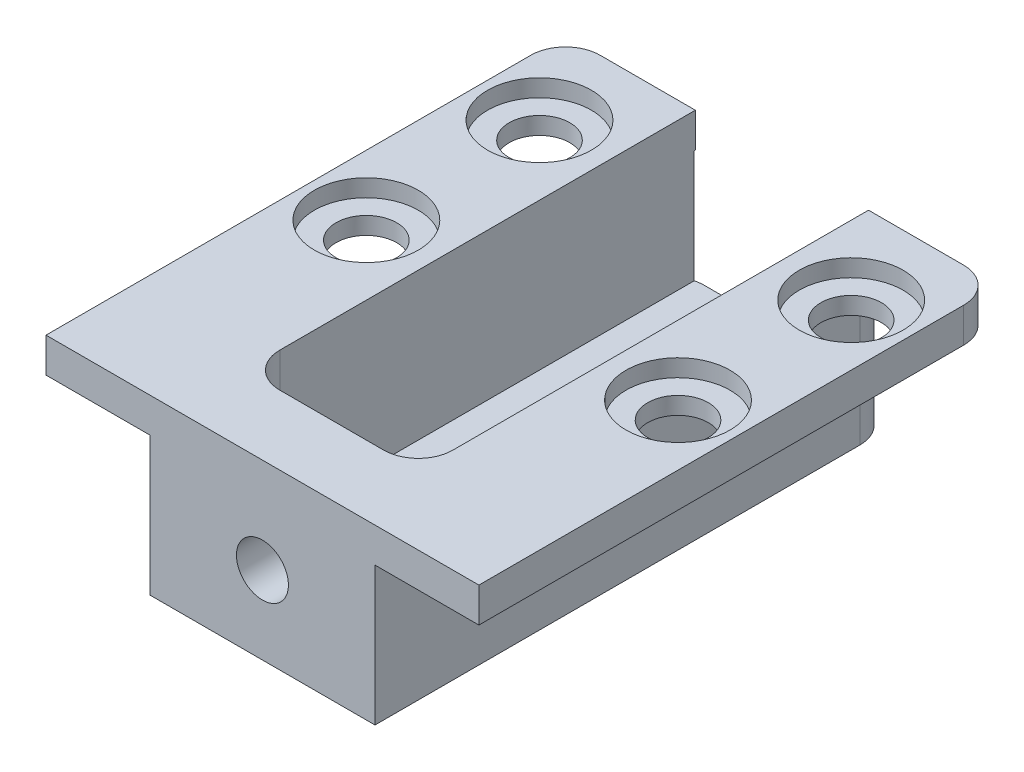
SolidWorks part; units mm, degrees
other "标注1"
sketch "草图19" plane through (-20.75, 4, 27.75) normal (0.0284, 0.9516, -0.306) x (-0.8925, -0.1137, -0.4365)
ref_plane "前视基准面" through (0, 0, 0) normal (0, 0, 1) x (1, 0, 0)
ref_plane "上视基准面" through (0, 0, 0) normal (0, 1, 0) x (1, 0, 0)
ref_plane "右视基准面" through (0, 0, 0) normal (1, 0, 0) x (0, 0, -1)
sketch "草图1" plane through (0, 0, 0) normal (0, 1, 0) x (1, 0, 0)
  line L1 (-17.5, -27.5) -> (17.5, -27.5)
  line L2 (-17.5, -27.5) -> (-17.5, 27.5)
  line L3 (-17.5, 27.5) -> (17.5, 27.5)
  line L4 (17.5, -27.5) -> (17.5, 27.5)
  line L5 (-17.5, -27.5) -> (17.5, 27.5) construction
  line L6 (-17.5, 27.5) -> (17.5, -27.5) construction
  point P0 (0, 0)
  dimension "D1" = 55
  dimension "D2" = 35
extrude "凸台-拉伸1" add sketch "草图1" along normal blind 1
sketch "草图2" plane through (0, 1, 0) normal (0, 1, 0) x (1, 0, 0)
  line L0 (-105.917, 0) -> (-62.25, 0) construction
  line L1 (106.75, 2.25) -> (121.75, 2.25)
  line L2 (-31.4474, 57.1013) -> (151.75, 26.6691)
  line L4 (124.0586, 2.6571) -> (154.0586, 13.5762)
  line L5 (-60.1618, 23.6059) -> (-42.6093, 52.0296)
  line L6 (121.75, 2.25) -> (121.75, 9) construction
  line L7 (121.75, -2.25) -> (121.75, -9) construction
  line L8 (-60.1618, -23.6059) -> (-42.6093, -52.0296)
  line L9 (124.0586, -2.6571) -> (154.0586, -13.5762)
  line L10 (121.75, -9) -> (128.5, -9)
  line L11 (-31.4474, -57.1013) -> (151.75, -26.6691)
  line L12 (106.75, -2.25) -> (121.75, -2.25)
  line L13 (-62.25, 16.25) -> (-62.25, -16.25)
  line L14 (106.75, 2.25) -> (106.75, -2.25)
  line L15 (106.75, 0) -> (124.0666, 0) construction
  arc A0 (-60.1618, 23.6059) -> (-62.25, 16.25) centre (-48.25, 16.25) ccw
  arc A1 (-31.4474, 57.1013) -> (-42.6093, 52.0296) centre (-33.25, 46.25) ccw
  arc A2 (121.75, 2.25) -> (124.0586, 2.6571) centre (121.75, 9) ccw
  arc A3 (154.0586, 13.5762) -> (151.75, 26.6691) centre (151.75, 19.9191) ccw
  arc A4 (154.0586, -13.5762) -> (151.75, -26.6691) centre (151.75, -19.9191) cw
  arc A5 (121.75, -2.25) -> (128.5, -9) centre (121.75, -9) cw
  arc A6 (-31.4474, -57.1013) -> (-42.6093, -52.0296) centre (-33.25, -46.25) cw
  arc A7 (-60.1618, -23.6059) -> (-62.25, -16.25) centre (-48.25, -16.25) cw
  line M10 (17.5, -27.5) -> (17.5, 27.5)
  line M11 (17.5, 27.5) -> (-17.5, 27.5)
  line M12 (-17.5, 27.5) -> (-17.5, -27.5)
  line M13 (-17.5, -27.5) -> (17.5, -27.5)
  dimension "D2" = 28
  dimension "D3" = 48.25
  dimension "D4" = 22
  dimension "D5" = 15
  dimension "D7" = 13.5
  dimension "D10" = 13.5
  dimension "D11" = 30
  dimension "D1" = 2.25
  dimension "D8" = 20
  dimension "D9" = 30
  dimension "D12" = 15
extrude "凸台-拉伸2" add sketch "草图2" along normal blind 3 contours A7 L8 A6 L11 A4 L9 A5 L12 L14 L1 A2 L4 A3 L2 A1 L5 A0 L13 | M13 M10 M11 M12 region at (37.3678, 1, 0) region at (0, 1, 0)
sketch "草图3" plane through (0, 4, 0) normal (0, 1, 0) x (1, 0, 0)
  circle A0 centre (-48.25, 16.25) radius 5
  circle A1 centre (-48.25, -16.25) radius 5
  circle A2 centre (-33.25, 46.25) radius 6.6982
  circle A3 centre (151.75, 19.9191) radius 2.5794
  circle A4 centre (121.75, 9) radius 2.5794
  circle A5 centre (121.75, -9) radius 2.5794
  circle A6 centre (151.75, -19.9191) radius 2.5794
  circle A7 centre (-33.25, -46.25) radius 6.6982
  dimension "D1" = 10
extrude "切除-拉伸1" cut sketch "草图3" against normal through all contours A0 | A1 region at (-48.25, 4, -16.25)
sketch "草图4" plane through (0, 4, 0) normal (0, 1, 0) x (1, 0, 0)
  circle A0 centre (-33.25, 46.25) radius 4
  circle A1 centre (-33.25, -46.25) radius 4
  dimension "D1" = 8
  dimension "D2" = 8
extrude "切除-拉伸2" cut sketch "草图4" against normal blind 2
sketch "草图5" plane through (0, 4, 0) normal (0, 1, 0) x (1, 0, 0)
  circle A0 centre (121.75, 9) radius 2
  circle A1 centre (121.75, -9) radius 2
  circle A2 centre (151.75, 19.9191) radius 2
  circle A3 centre (151.75, -19.9191) radius 2
  dimension "D1" = 4
extrude "切除-拉伸3" cut sketch "草图5" against normal blind 2
sketch "草图8" plane through (0, 1, 0) normal (0, -1, 0) x (1, 0, 0)
  line L1 (-39.75, -26.25) -> (-26.75, -26.25)
  line L2 (-39.75, -26.25) -> (-39.75, -66.25)
  line L3 (-39.75, -66.25) -> (-26.75, -66.25)
  line L4 (-26.75, -26.25) -> (-26.75, -66.25)
  line L5 (-39.75, -26.25) -> (-26.75, -66.25) construction
  line L6 (-39.75, -66.25) -> (-26.75, -26.25) construction
  line L16 (124.0586, 2.6571) -> (154.0586, 13.5762)
  line L17 (151.75, 26.6691) -> (-31.4474, 57.1013)
  line L18 (-42.6093, 52.0296) -> (-60.1618, 23.6059)
  line L19 (-62.25, 16.25) -> (-62.25, -16.25)
  line L20 (-60.1618, -23.6059) -> (-42.6093, -52.0296)
  line L21 (-31.4474, -57.1013) -> (151.75, -26.6691)
  line L22 (154.0586, -13.5762) -> (124.0586, -2.6571)
  line L23 (121.75, -2.25) -> (106.75, -2.25)
  line L24 (106.75, -2.25) -> (106.75, 2.25)
  line L25 (106.75, 2.25) -> (121.75, 2.25)
  line L26 (124.0586, 2.6571) -> (154.0586, 13.5762)
  line L27 (151.75, 26.6691) -> (-31.4474, 57.1013)
  line L28 (-42.6093, 52.0296) -> (-60.1618, 23.6059)
  line L31 (-31.4474, -57.1013) -> (151.75, -26.6691)
  line L32 (154.0586, -13.5762) -> (124.0586, -2.6571)
  line L33 (121.75, -2.25) -> (106.75, -2.25)
  line L34 (106.75, -2.25) -> (106.75, 2.25)
  line L35 (106.75, 2.25) -> (121.75, 2.25)
  arc A8 (154.0586, 13.5762) -> (151.75, 26.6691) centre (151.75, 19.9191) ccw
  arc A9 (-31.4474, 57.1013) -> (-42.6093, 52.0296) centre (-33.25, 46.25) ccw
  arc A10 (-60.1618, 23.6059) -> (-62.25, 16.25) centre (-48.25, 16.25) ccw
  arc A11 (-62.25, -16.25) -> (-60.1618, -23.6059) centre (-48.25, -16.25) ccw
  arc A12 (-42.6093, -52.0296) -> (-31.4474, -57.1013) centre (-33.25, -46.25) ccw
  arc A13 (151.75, -26.6691) -> (154.0586, -13.5762) centre (151.75, -19.9191) ccw
  arc A14 (124.0586, -2.6571) -> (121.75, -2.25) centre (121.75, -9) ccw
  arc A15 (121.75, 2.25) -> (124.0586, 2.6571) centre (121.75, 9) ccw
  arc A16 (154.0586, 13.5762) -> (151.75, 26.6691) centre (151.75, 19.9191) ccw
  arc A17 (-31.4474, 57.1013) -> (-42.6093, 52.0296) centre (-33.25, 46.25) ccw
  arc A18 (-60.1618, 23.6059) -> (-62.25, 16.25) centre (-48.25, 16.25) ccw
  arc A19 (-62.25, -16.25) -> (-60.1618, -23.6059) centre (-48.25, -16.25) ccw
  arc A20 (-42.6093, -52.0296) -> (-31.4474, -57.1013) centre (-33.25, -46.25) ccw
  arc A21 (151.75, -26.6691) -> (154.0586, -13.5762) centre (151.75, -19.9191) ccw
  arc A22 (124.0586, -2.6571) -> (121.75, -2.25) centre (121.75, -9) ccw
  arc A23 (121.75, 2.25) -> (124.0586, 2.6571) centre (121.75, 9) ccw
  point P0 (-33.25, -46.25)
  arc M32 (-42.6093, -52.0296) -> (-31.4474, -57.1013) centre (-33.25, -46.25) ccw
  line M33 (-31.4474, -57.1013) -> (151.75, -26.6691)
  dimension "D1" = 13
  dimension "D2" = 40
  dimension "D3" = 0
extrude "凸台-拉伸3" add sketch "草图8" along normal blind 7 contours L4 L1 L2 M32 M33 region at (-33.2258, 1, -41.4837)
mirror "镜向1" about plane through (0, 0, 0) normal (0, 0, 1) of "凸台-拉伸3"
sketch "草图9" plane through (0, -6, 0) normal (0, -1, 0) x (1, 0, 0)
  line L0 (-39.75, -26.25) -> (-26.75, -26.25) construction
  line L2 (-38.25, -53.75) -> (-38.25, -27.75)
  line L3 (-38.25, -27.75) -> (-28.25, -27.75)
  line L4 (-28.25, -53.75) -> (-28.25, -27.75)
  line L5 (-35.5448, -54.7408) -> (-28.25, -27.75) construction
  line L6 (-38.25, -27.75) -> (-31.223, -53.75) construction
  line L8 (-28.25, -53.75) -> (-38.25, -53.75)
  point P0 (-33.25, -46.25)
  dimension "D1" = 10
  dimension "D2" = 1.5
  dimension "D3" = 26
extrude "切除-拉伸4" cut sketch "草图9" against normal through all from offset 1.5 offset against normal yes
mirror "镜向2" about plane through (0, 0, 0) normal (0, 0, 1) of "切除-拉伸4"
sketch "草图10" plane through (0, 0, -53.75) normal (0, 0, 1) x (1, 0, 0)
  line L4 (-38.25, -4.5) -> (-28.25, -4.5)
  line L5 (-28.25, -4.5) -> (-28.25, 4)
  line L6 (-28.25, 4) -> (-38.25, 4)
  line L7 (-38.25, 4) -> (-38.25, -4.5)
  line L8 (-38.25, -4.5) -> (-28.25, -4.5)
  line L9 (-28.25, -4.5) -> (-28.25, 4)
  line L10 (-28.25, 4) -> (-38.25, 4)
  line L11 (-38.25, 4) -> (-38.25, -4.5)
  circle A0 centre (-33.25, -1.5) radius 1.5
  dimension "D2" = 3
  dimension "D3" = 3
  dimension "D1" = 0
extrude "切除-拉伸5" cut sketch "草图10" against normal through all contours A0 region at (-33.25, -1.5, -53.75)
mirror "镜向3" about plane through (0, 0, 0) normal (0, 0, 1) of "切除-拉伸5"
sketch "草图11" plane through (0, -6, 0) normal (0, -1, 0) x (1, 0, 0)
  line L4 (-26.75, 26.25) -> (-26.75, 56.321)
  line L5 (-26.75, 56.321) -> (-31.4474, 57.1013)
  line L6 (-39.75, 55.1241) -> (-39.75, 26.25)
  line L7 (-39.75, 26.25) -> (-26.75, 26.25)
  line L8 (-26.75, 26.25) -> (-26.75, 56.321)
  line L9 (-26.75, 56.321) -> (-31.4474, 57.1013)
  line L10 (-39.75, 55.1241) -> (-39.75, 26.25)
  line L11 (-39.75, 26.25) -> (-26.75, 26.25)
  line L13 (-135.5056, -159.1164) -> (202.8718, -159.1164)
  line L14 (-135.5056, -159.1164) -> (-135.5056, 159.1164)
  line L15 (-135.5056, 159.1164) -> (202.8718, 159.1164)
  line L16 (-20.75, 20.25) -> (-20.75, 61.4065)
  line L17 (-20.75, 61.4065) -> (-30.4642, 63.0202)
  line L18 (-45.75, 57.7717) -> (-45.75, 20.25)
  line L19 (-45.75, 20.25) -> (-20.75, 20.25)
  line L20 (-20.75, 20.25) -> (-20.75, 61.4065)
  line L21 (-20.75, 61.4065) -> (-30.4642, 63.0202)
  line L22 (-45.75, 57.7717) -> (-45.75, 20.25)
  line L23 (-45.75, 20.25) -> (-20.75, 20.25)
  line L24 (202.8718, -159.1164) -> (202.8718, 159.1164)
  line L25 (-135.5056, -159.1164) -> (202.8718, 159.1164) construction
  line L26 (-135.5056, 159.1164) -> (202.8718, -159.1164) construction
  arc A1 (-31.4474, 57.1013) -> (-39.75, 55.1241) centre (-33.25, 46.25) ccw
  arc A2 (-31.4474, 57.1013) -> (-39.75, 55.1241) centre (-33.25, 46.25) ccw
  arc A4 (-30.4642, 63.0202) -> (-45.75, 57.7717) centre (-33.25, 46.25) ccw
  arc A5 (-30.4642, 63.0202) -> (-45.75, 57.7717) centre (-33.25, 46.25) ccw
  point P4 (33.6831, 0)
  dimension "D1" = 0
  dimension "D2" = 6
extrude "切除-拉伸6" cut sketch "草图11" along direction (0, 1, 0) on the side against the normal up to surface (10 mm away) contours L13 L24 L15 L14 A5 L21 L20 L23 L22 region at (34.3371, -6, -0.4026) up to face at (51.7917, 4, 0)
sketch "草图12" plane through (0, 4, 0) normal (0, 1, 0) x (1, 0, 0)
  line L0 (-28.25, -27.75) -> (-38.25, -27.75) construction
  line L1 (-20.75, -20.25) -> (-53.7738, -20.25)
  line L2 (-20.75, -20.25) -> (-20.75, -27.75)
  line L3 (-20.75, -27.75) -> (-53.7738, -27.75)
  line L4 (-53.7738, -20.25) -> (-53.7738, -27.75)
extrude "切除-拉伸7" cut sketch "草图12" against normal through all
sketch "草图13" plane through (0, 1, 0) normal (0, -1, 0) x (1, 0, 0)
  line L4 (-26.75, 56.321) -> (-26.75, 27.75)
  line L5 (-26.75, 27.75) -> (-20.75, 27.75)
  line L6 (-20.75, 27.75) -> (-20.75, 55.3243)
  line L7 (-20.75, 55.3243) -> (-26.75, 56.321)
  line L8 (-26.75, 56.321) -> (-26.75, 27.75)
  line L9 (-26.75, 27.75) -> (-20.75, 27.75)
  line L10 (-20.75, 27.75) -> (-20.75, 55.3243)
  line L11 (-20.75, 55.3243) -> (-26.75, 56.321)
  line L12 (-45.75, 46.9437) -> (-45.75, 27.75)
  line L13 (-45.75, 27.75) -> (-39.75, 27.75)
  line L14 (-39.75, 27.75) -> (-39.75, 55.1241)
  line L15 (-42.6093, 52.0296) -> (-45.75, 46.9437)
  line L16 (-45.75, 46.9437) -> (-45.75, 27.75)
  line L17 (-45.75, 27.75) -> (-39.75, 27.75)
  line L18 (-39.75, 27.75) -> (-39.75, 55.1241)
  line L19 (-42.6093, 52.0296) -> (-45.75, 46.9437)
  arc A1 (-39.75, 55.1241) -> (-42.6093, 52.0296) centre (-33.25, 46.25) ccw
  arc A2 (-39.75, 55.1241) -> (-42.6093, 52.0296) centre (-33.25, 46.25) ccw
  dimension "D1" = 0
  dimension "D2" = 0
extrude "切除-拉伸8" cut sketch "草图13" along normal blind 10 from offset 1 offset against normal yes
sketch "草图14" plane through (0, 4, 0) normal (0, 1, 0) x (1, 0, 0)
  line L1 (-20.75, -27.75) -> (-45.75, -27.75)
  line L2 (-20.75, -27.75) -> (-20.75, -57.75)
  line L3 (-20.75, -57.75) -> (-45.75, -57.75)
  line L4 (-45.75, -27.75) -> (-45.75, -57.75)
  line L9 (-38.25, -27.75) -> (-45.75, -27.75)
  line L10 (-45.75, -27.75) -> (-45.75, -46.9437)
  line L11 (-45.75, -46.9437) -> (-42.6093, -52.0296)
  line L12 (-31.4474, -57.1013) -> (-20.75, -55.3243)
  line L13 (-20.75, -55.3243) -> (-20.75, -27.75)
  line L14 (-20.75, -27.75) -> (-28.25, -27.75)
  line L15 (-28.25, -27.75) -> (-28.25, -53.75)
  line L16 (-28.25, -53.75) -> (-38.25, -53.75)
  line L17 (-38.25, -53.75) -> (-38.25, -27.75)
  line L18 (-38.25, -27.75) -> (-45.75, -27.75)
  line L19 (-45.75, -27.75) -> (-45.75, -46.9437)
  line L20 (-45.75, -46.9437) -> (-42.6093, -52.0296)
  line L21 (-31.4474, -57.1013) -> (-20.75, -55.3243)
  line L22 (-20.75, -55.3243) -> (-20.75, -27.75)
  line L23 (-20.75, -27.75) -> (-28.25, -27.75)
  line L24 (-28.25, -27.75) -> (-28.25, -53.75)
  line L25 (-28.25, -53.75) -> (-38.25, -53.75)
  line L26 (-38.25, -53.75) -> (-38.25, -27.75)
  arc A1 (-42.6093, -52.0296) -> (-31.4474, -57.1013) centre (-33.25, -46.25) ccw
  arc A2 (-42.6093, -52.0296) -> (-31.4474, -57.1013) centre (-33.25, -46.25) ccw
  line M12 (-38.25, -27.75) -> (-45.75, -27.75)
  line M13 (-45.75, -27.75) -> (-45.75, -46.9437)
  line M14 (-45.75, -46.9437) -> (-42.6093, -52.0296)
  arc M15 (-42.6093, -52.0296) -> (-31.4474, -57.1013) centre (-33.25, -46.25) ccw
  line M16 (-31.4474, -57.1013) -> (-20.75, -55.3243)
  line M17 (-20.75, -55.3243) -> (-20.75, -27.75)
  line M18 (-20.75, -27.75) -> (-28.25, -27.75)
  line M19 (-28.25, -27.75) -> (-28.25, -53.75)
  line M20 (-28.25, -53.75) -> (-38.25, -53.75)
  line M21 (-38.25, -53.75) -> (-38.25, -27.75)
  dimension "D2" = 30
  dimension "D1" = 0
extrude "凸台-拉伸4" add sketch "草图14" against normal up to surface (2 mm away) contours M21 M12 M13 M14 M15 M16 M17 M18 M19 M20 | L4 L3 L2 M14 M16 M15 region at (-21.1367, 4, 41.5371) region at (-21.0224, 4, 56.5371) up to face at (-23.75, 2, 41.7863)
sketch "草图15" plane through (0, -6, 0) normal (0, -1, 0) x (1, 0, 0)
  line L0 (-39.75, 55.1241) -> (-39.75, 57.75)
  line L1 (-20.75, 57.75) -> (-45.75, 57.75) construction
  line L2 (-26.75, 56.321) -> (-26.75, 57.75)
  line L3 (-39.75, 57.75) -> (-26.75, 57.75)
  line L8 (-39.75, 27.75) -> (-26.75, 27.75)
  line L9 (-26.75, 27.75) -> (-26.75, 56.321)
  line L10 (-26.75, 56.321) -> (-31.4474, 57.1013)
  line L11 (-39.75, 55.1241) -> (-39.75, 27.75)
  line L14 (-26.75, 56.321) -> (-31.4474, 57.1013)
  arc A1 (-31.4474, 57.1013) -> (-39.75, 55.1241) centre (-33.25, 46.25) ccw
  arc A2 (-31.4474, 57.1013) -> (-39.75, 55.1241) centre (-33.25, 46.25) ccw
  dimension "D1" = 0
extrude "凸台-拉伸5" add sketch "草图15" against normal up to surface (8 mm away) up to face at (-33.0719, 2, 43.9872)
sketch "草图16" plane through (0, 0, 53.75) normal (0, 0, -1) x (-1, 0, 0)
  circle A0 centre (33.25, -1.5) radius 1.5
extrude "切除-拉伸9" cut sketch "草图16" against normal through all
sketch "草图17" plane through (0, 4, 0) normal (0, 1, 0) x (1, 0, 0)
  line L0 (-28.25, -27.75) -> (-20.75, -27.75)
  line L1 (-45.75, -27.75) -> (-38.25, -27.75)
  line L2 (-33.25, -27.75) -> (-33.25, -43.8463)
  line L3 (-28.25, -27.75) -> (-38.25, -27.75) construction
  circle A0 centre (-24.25, -32.75) radius 1.75
  circle A1 centre (-24.25, -42.75) radius 1.75
  circle A2 centre (-42.25, -32.75) radius 1.75
  circle A3 centre (-42.25, -42.75) radius 1.75
  dimension "D1" = 3.5
  dimension "D2" = 5
  dimension "D3" = 10
  dimension "D4" = 5
  dimension "D5" = 10
  dimension "D6" = 18
  dimension "D7" = 9
extrude "切除-拉伸10" cut sketch "草图17" against normal blind 10 contours A0 | A1 | A3 | A2 region at (-24.25, 4, 32.75) region at (-24.25, 4, 42.75) region at (-42.25, 4, 32.75) region at (-42.25, 4, 42.75)
sketch "草图18" plane through (0, 4, 0) normal (0, 1, 0) x (1, 0, 0)
  circle A0 centre (-42.25, -32.75) radius 3
  circle A1 centre (-24.25, -32.75) radius 3
  circle A2 centre (-24.25, -42.75) radius 3
  circle A3 centre (-42.25, -42.75) radius 3
  dimension "D1" = 6
extrude "切除-拉伸11" cut sketch "草图18" against normal blind 1
fillet "圆角1" radius 2 1 edges at (-39.75, -2, 27.75)
fillet "圆角2" radius 2 2 edges at (-45.75, 3, 27.75) (-20.75, 3, 27.75)
fillet "圆角3" radius 2 1 edges at (-26.75, -2, 27.75)
fillet "圆角4" radius 2 2 edges at (-28.25, -0.25, 53.75) (-38.25, -0.25, 53.75)
